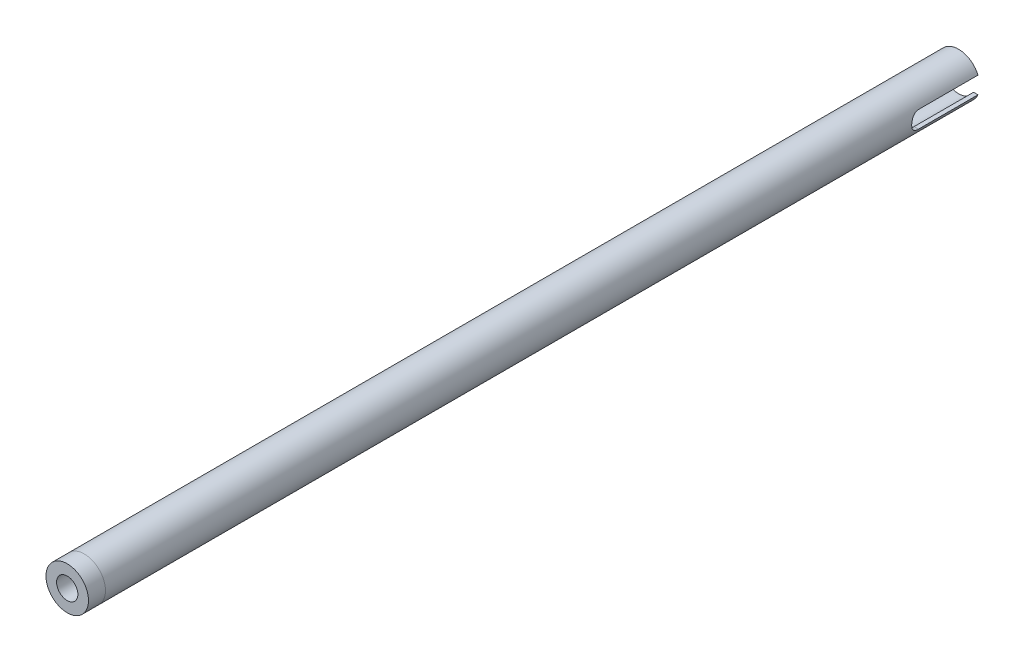
SolidWorks part; units mm, degrees
material "AISI 4130 Steel, normalized at 870C"
ref_plane "Front Plane" through (0, 0, 0) normal (0, 0, 1) x (1, 0, 0)
ref_plane "Top Plane" through (0, 0, 0) normal (0, 1, 0) x (1, 0, 0)
ref_plane "Right Plane" through (0, 0, 0) normal (1, 0, 0) x (0, 0, -1)
sketch "Axis" plane through (0, 0, 0) normal (0, 1, 0) x (1, 0, 0)
  line L0 (0, 0) -> (0, 332.6617) construction
  line L1 (0, 0) -> (0, -28.575) construction
  line L2 (0, 332.6617) -> (-7.9375, 332.6617) construction
  line L4 (0, 361.4136) -> (-10.3187, 324.0362) construction
  dimension "D1" = 28.575
  dimension "D2" = 7.9375
sketch "Sketch1" plane through (0, 0, 0) normal (0, 0, 1) x (1, 0, 0)
  line L0 (-7.9375, 0) -> (7.9375, 0) construction
  line L1 (-7.2748, 3.175) -> (7.2748, 3.175)
  line L2 (-7.2748, -3.175) -> (7.2748, -3.175)
  circle A0 centre (0, 0) radius 7.9375
  circle A1 centre (0, 0) radius 6.4643
  circle A2 centre (0, 0) radius 3.9688
  dimension "D1" = 15.875
  dimension "D3" = 7.9375
  dimension "D2" = 1.4732
  dimension "D4" = 6.35
extrude "Threaded insert 1-1" add sketch "Sketch1" against normal blind 6.35 contours A2 L1 A1 | A1 L1 A0 | A2 L0 A1 L1 | A1 L0 A0 L1 | L0 A1 L2 A0 | L0 A2 L2 A1 | A2 L2 A1 | A1 L2 A0 | L0 A1 L2 A2 | L0 A0 L2 A1 | A0 L0 A1 L1 | A1 L0 A2 L1 region at (4.8156, 1.6537, 0) region at (4.8156, -1.6537, 0) region at (6.9501, 1.6161, 0) region at (6.9501, -1.6161, 0) region at (-4.8156, -1.6537, 0) region at (-4.8156, 1.6537, 0) region at (0, 4.6361, 0) region at (0, -4.6361, 0) region at (0, 6.6174, 0) region at (6.4528, -3.3281, 0) region at (-6.9501, -1.6161, 0) region at (-6.9501, 1.6161, 0)
extrude "Threaded insert 1-2" add sketch "Sketch1<3>" against normal blind 9.525 from surface contours A2 L1 A1 | A2 L0 A1 L1 | L0 A2 L2 A1 | A2 L2 A1 | L0 A1 L2 A2 | A1 L0 A2 L1 region at (4.8156, 1.6537, 0) region at (4.8156, -1.6537, 0) region at (-4.8156, -1.6537, 0) region at (-4.8156, 1.6537, 0) region at (0, 4.6361, 0) region at (0, -4.6361, 0) starting at face at (7.9375, 0, -6.35)
sketch "Sketch1<3>" plane through (0, 0, 0) normal (0, 0, 1) x (1, 0, 0) same geometry as "Sketch1"
extrude "A-arm tube" add sketch "Sketch1<4>" against normal up to vertex (332.6617 mm away) from surface separate body contours A1 L1 A0 | A1 L0 A0 L1 | L0 A1 L2 A0 | A1 L2 A0 | L0 A0 L2 A1 | A0 L0 A1 L1 region at (6.9501, 1.6161, 0) region at (6.9501, -1.6161, 0) region at (0, 6.6174, 0) region at (6.4528, -3.3281, 0) region at (-6.9501, -1.6161, 0) region at (-6.9501, 1.6161, 0) up to point (0, 0, -332.6617) starting at face at (6.4643, 0, -6.35)
sketch "Sketch1<4>" plane through (0, 0, 0) normal (0, 0, 1) x (1, 0, 0) same geometry as "Sketch1"
extrude "Apex slot" cut sketch "Sketch1<5>" along normal blind 25.4 from surface contours A0 L0 A1 L1 | L0 A0 L2 A1 | A1 L0 A0 L1 | L0 A1 L2 A0 region at (6.9501, 1.6161, 0) region at (6.9501, -1.6161, 0) region at (-6.9501, -1.6161, 0) region at (-6.9501, 1.6161, 0) starting at face at (6.4643, 0, -332.6617)
sketch "Sketch1<5>" plane through (0, 0, 0) normal (0, 0, 1) x (1, 0, 0) same geometry as "Sketch1"
fillet "Fillet1" radius 3.175 4 edges at (-6.4528, 3.175, -307.2617) (-6.4528, -3.175, -307.2617) (6.4528, -3.175, -307.2617) (6.4528, 3.175, -307.2617)
equation "\"tube diameter\"= 5 / 8"
equation "\"tube thickness\"= .058"
equation "\"apex thickness\"= .25"
equation "\"tube slot\"= 1"
equation "\"D1@Sketch1\"=\"tube diameter\""
equation "\"D2@Sketch1\"=\"tube thickness\""
equation "\"threaded insert hole\"= .3125"
equation "\"D3@Sketch1\"=\"threaded insert hole\""
equation "\"D4@Sketch1\"=\"apex thickness\""
equation "\"D1@Apex slot\" = \"tube slot\""
equation "\"D1@Fillet1\"=\"apex thickness\"/2"
equation "\"D2@Axis\"=\"tube diameter\"/2"
